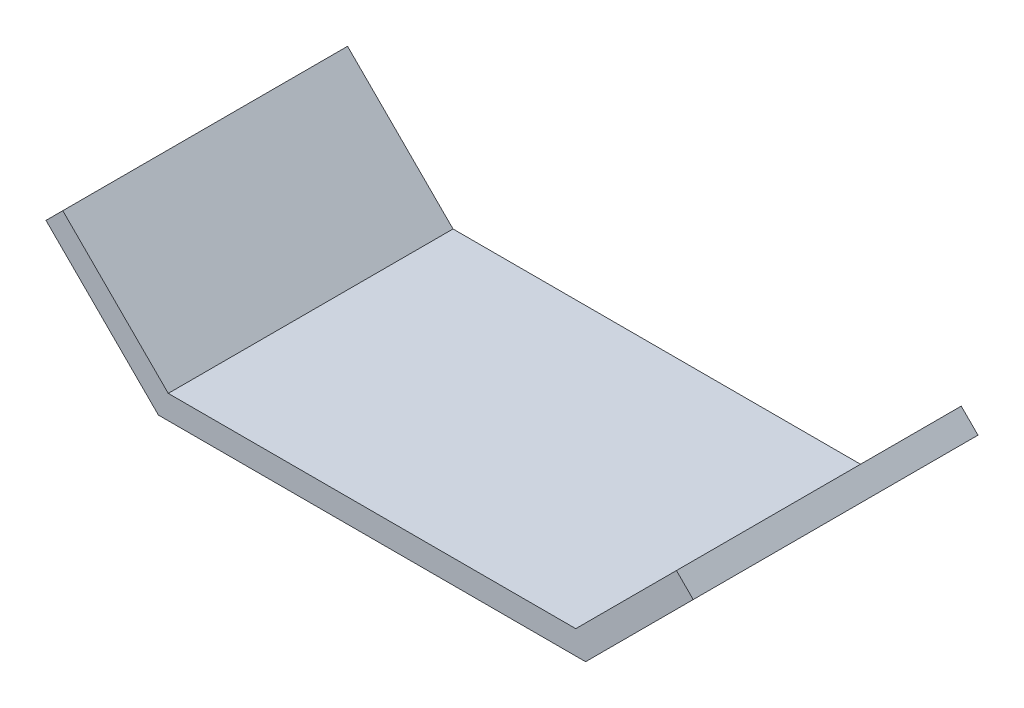
SolidWorks part; units mm, degrees
ref_plane "前视基准面" through (0, 0, 0) normal (0, 0, 1) x (1, 0, 0)
ref_plane "上视基准面" through (0, 0, 0) normal (0, 1, 0) x (1, 0, 0)
ref_plane "右视基准面" through (0, 0, 0) normal (1, 0, 0) x (0, 0, -1)
other "Configuration Table"
sketch "草图1" plane through (0, 0, 0) normal (0, 0, 1) x (1, 0, 0)
  line L0 (-45, -2.5) -> (-68.6879, 21.1879)
  line L1 (-45, -2.5) -> (45, -2.5)
  line L2 (-45, -2.5) -> (-45, 2.5)
  line L3 (-45, 2.5) -> (45, 2.5)
  line L4 (45, -2.5) -> (45, 2.5)
  line L5 (-45, -2.5) -> (45, 2.5) construction
  line L6 (-45, 2.5) -> (45, -2.5) construction
  line L7 (-68.6879, 21.1879) -> (-65.1524, 24.7234)
  line L8 (-42.9289, 2.5) -> (-65.1524, 24.7234)
  line L9 (45, -2.5) -> (67.6777, 20.1777)
  line L10 (67.6777, 20.1777) -> (64.1421, 23.7132)
  line L11 (64.1421, 23.7132) -> (42.9289, 2.5)
  point P0 (0, 0)
  dimension "D1" = 5
  dimension "D2" = 90
  dimension "D3" = 135
  dimension "D4" = 5
  dimension "D5" = 30
  dimension "D6" = 5
  dimension "D7" = 30
  dimension "D8" = 135
extrude "凸台-拉伸1" add sketch "草图1" along normal mid plane 60 contours L3 L8 L7 L0 L2 | L1 L4 L3 L2 | L10 L11 L3 L4 L9 region at (0, 0, 0) region at (-55.8245, 11.8051, 0) region at (55.3202, 11.2982, 0)
